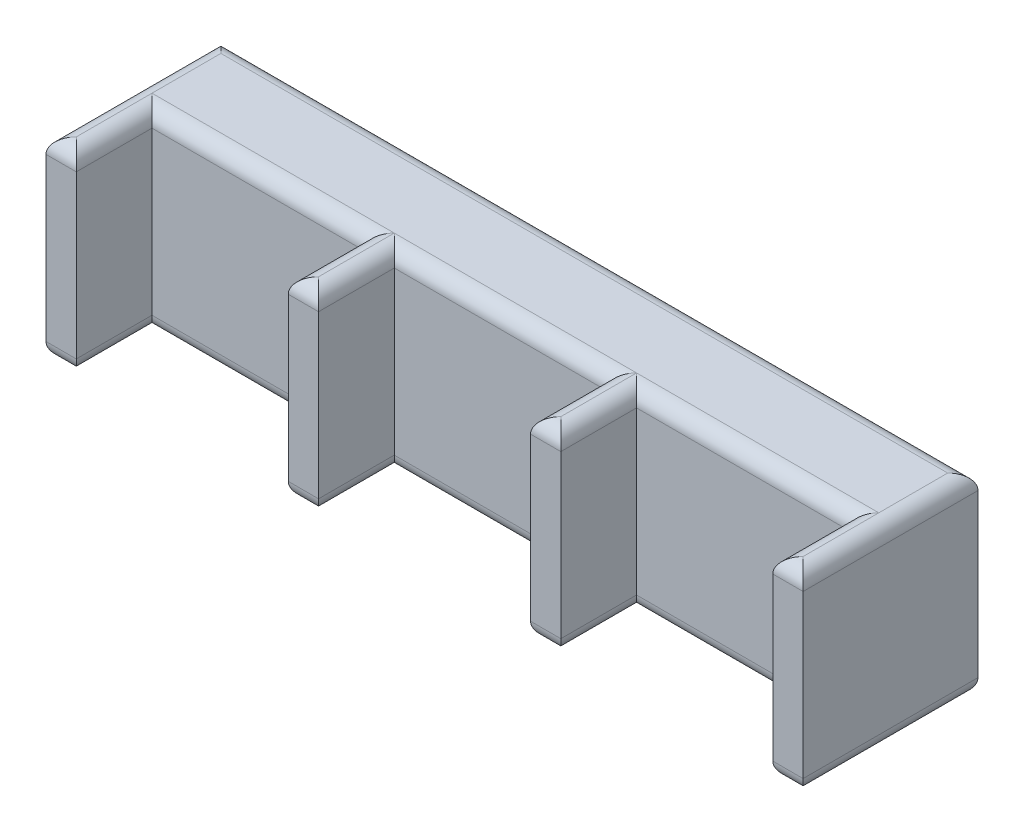
SolidWorks part; units mm, degrees
ref_plane "Front Plane" through (0, 0, 0) normal (0, 0, 1) x (1, 0, 0)
ref_plane "Top Plane" through (0, 0, 0) normal (0, 1, 0) x (1, 0, 0)
ref_plane "Right Plane" through (0, 0, 0) normal (1, 0, 0) x (0, 0, -1)
sketch "Sketch1" plane through (0, 0, 0) normal (0, 0, 1) x (1, 0, 0)
  line L1 (25, -6.35) -> (-25, -6.35)
  line L2 (25, -6.35) -> (25, 6.35)
  line L3 (25, 6.35) -> (-25, 6.35)
  line L4 (-25, -6.35) -> (-25, 6.35)
  line L5 (25, -6.35) -> (-25, 6.35) construction
  line L6 (25, 6.35) -> (-25, -6.35) construction
  point P0 (0, 0)
  dimension "D1" = 12.7
  dimension "D2" = 50
extrude "Boss-Extrude1" add sketch "Sketch1" along normal blind 6.55
sketch "Sketch2" plane through (0, 0, 0) normal (0, 0, -1) x (-1, 0, 0)
  line L1 (24, -3.16) -> (-24, -3.16)
  line L2 (24, -3.16) -> (24, 3.16)
  line L3 (24, 3.16) -> (-24, 3.16)
  line L4 (-24, -3.16) -> (-24, 3.16)
  line L5 (24, -3.16) -> (-24, 3.16) construction
  line L6 (24, 3.16) -> (-24, -3.16) construction
  point P0 (0, 0)
  dimension "D1" = 48
  dimension "D2" = 6.32
extrude "Cut-Extrude2" cut sketch "Sketch2" against normal blind 6.35
sketch "Sketch3" plane through (0, 0, 6.55) normal (0, 0, 1) x (1, 0, 0)
  line L0 (-25, -6.35) -> (25, -6.35) construction
  line L1 (-25, 6.35) -> (-23, 6.35)
  line L2 (-25, 6.35) -> (-25, -6.35)
  line L3 (-25, -6.35) -> (-23, -6.35)
  line L4 (-23, 6.35) -> (-23, -6.35)
  dimension "D1" = 2
extrude "Boss-Extrude2" add sketch "Sketch3" along normal blind 5
pattern_linear "LPattern1" count 4 spacing 16 along (1, 0, 0) of "Boss-Extrude2"
fillet "Fillet1" radius 1 32 edges at (-25, -6.35, 5.775) (-24, -6.35, 11.55) (-23, -6.35, 9.05) (-16, -6.35, 6.55) (-9, -6.35, 9.05) (-8, -6.35, 11.55) (-7, -6.35, 9.05) (0, -6.35, 6.55) (7, -6.35, 9.05) (8, -6.35, 11.55) (9, -6.35, 9.05) (16, -6.35, 6.55) (23, -6.35, 9.05) (24, -6.35, 11.55) (25, -6.35, 5.775) (0, -6.35, 0) (25, 6.35, 5.775) (24, 6.35, 11.55) (23, 6.35, 9.05) (16, 6.35, 6.55) (9, 6.35, 9.05) (8, 6.35, 11.55) (7, 6.35, 9.05) (0, 6.35, 6.55) (-7, 6.35, 9.05) (-8, 6.35, 11.55) (-9, 6.35, 9.05) (-16, 6.35, 6.55) (-23, 6.35, 9.05) (-24, 6.35, 11.55) (-25, 6.35, 5.775) (0, 6.35, 0)
